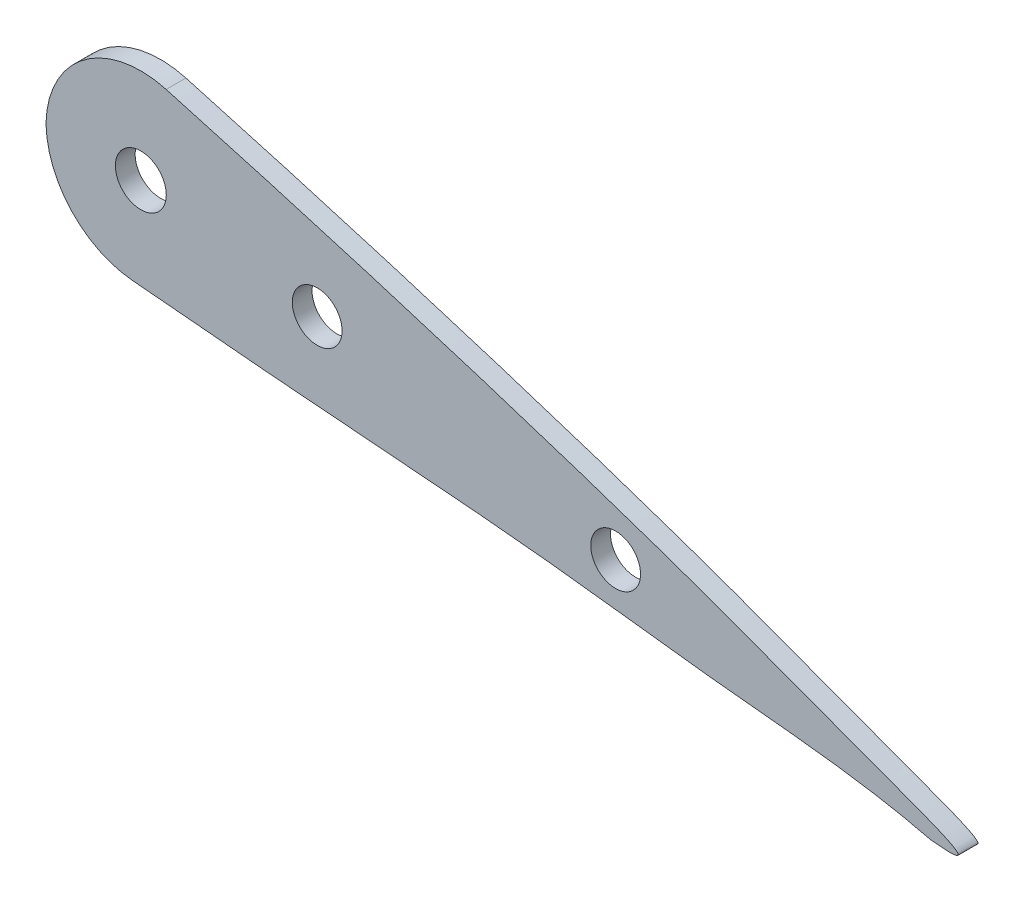
SolidWorks part; units mm, degrees
material "Balsa"
ref_plane "Front Plane" through (0, 0, 0) normal (0, 0, 1) x (1, 0, 0)
ref_plane "Top Plane" through (0, 0, 0) normal (0, 1, 0) x (1, 0, 0)
ref_plane "Right Plane" through (0, 0, 0) normal (1, 0, 0) x (0, 0, -1)
sketch "Sketch1" plane through (0, 0, 0) normal (0, 0, 1) x (1, 0, 0)
  spline S0 degree 3 poles (0.0006, 0.0001) (0.8106, 7.3592) (8.6491, 17.8566) (26.2867, 29.9752) (52.1111, 42.0692) (89.5976, 49.2908) (131.4008, 47.8848) (173.2567, 40.0411) (217.9611, 29.613) (256.9521, 19.5289) (290.3598, 8.711) (301.2732, 4.3828) (314.8169, -0.5162) (309.8463, 0.0001) knots 0 0 0 0 0.060864 0.113688 0.188609 0.312909 0.448482 0.557612 0.691544 0.852438 0.929756 0.976058 1 1 1 1
  spline S1 degree 3 poles (309.8463, 0.0001) (303.9568, 1.471) (293.9895, 2.094) (276.264, 4.5144) (260.8463, 5.4274) (235.8588, 7.8703) (205.1014, 8.8381) (157.7186, 9.0307) (110.4973, 6.1815) (66.5062, -0.5867) (36.4547, -6.0985) (15.3166, -6.1891) (1.2307, -6.9241) (0.0006, 0.0001) knots 0 0 0 0 0.057787 0.095275 0.171021 0.205339 0.335319 0.464904 0.658702 0.785512 0.893517 0.943092 1 1 1 1
extrude "Boss-Extrude1" add sketch "Sketch1" along normal blind 1.5875
sketch "Sketch2" plane through (0, 0, 1.5875) normal (0, 0, 1) x (1, 0, 0)
  circle A0 centre (20.32, 10.16) radius 6.35
  circle A1 centre (227.2963, 19.0501) radius 3.175
  dimension "D2" = 12.7
  dimension "D3" = 6.35
  dimension "D6" = 20.32
  dimension "D1" = 82.55
  dimension "D4" = 19.05
  dimension "D5" = 10.16
extrude "Cut-Extrude1" cut sketch "Sketch2" against normal through all
sketch "Sketch3" plane through (0, 0, 1.5875) normal (0, 0, 1) x (1, 0, 0)
  line L11 (-90.3395, -69.7561) -> (238.7263, -69.7561)
  line L12 (-90.3395, -69.7561) -> (-90.3395, 107.5465)
  line L13 (-90.3395, 107.5465) -> (238.7263, 107.5465)
  line L14 (238.7263, -69.7561) -> (238.7263, 107.5465)
  circle A1 centre (227.2963, 19.0501) radius 3.175 construction
  dimension "D1" = 11.43
extrude "Cut-Extrude2" cut sketch "Sketch3" against normal through all contours L14 L13 L12 L11
fillet "Fillet1" radius 7.62 2 edges at (238.7263, 7.3795, 0.7937) (238.7263, 24.1211, 0.7937)
sketch "Sketch4" plane through (0, 0, 1.5875) normal (0, 0, 1) x (1, 0, 0)
  circle A0 centre (246.3463, 14.163) radius 2.0447
  dimension "D1" = 4.0894
  dimension "D2" = 63.5
  dimension "D3" = 14.1628
extrude "Cut-Extrude3" cut sketch "Sketch4" against normal blind 2.54
sketch "Sketch5" plane through (0, 0, 1.5875) normal (0, 0, 1) x (1, 0, 0)
  circle A0 centre (260.5155, 11.7694) radius 2
  circle A1 centre (284.4955, 6.8346) radius 2
  point P4 (284.4955, 6.8346)
  point P5 (260.5155, 11.7694)
  dimension "D1" = 4
extrude "Cut-Extrude4" cut sketch "Sketch5" against normal blind 2.54
equation "\"D1@Sketch3\"=0.25+0.2"
